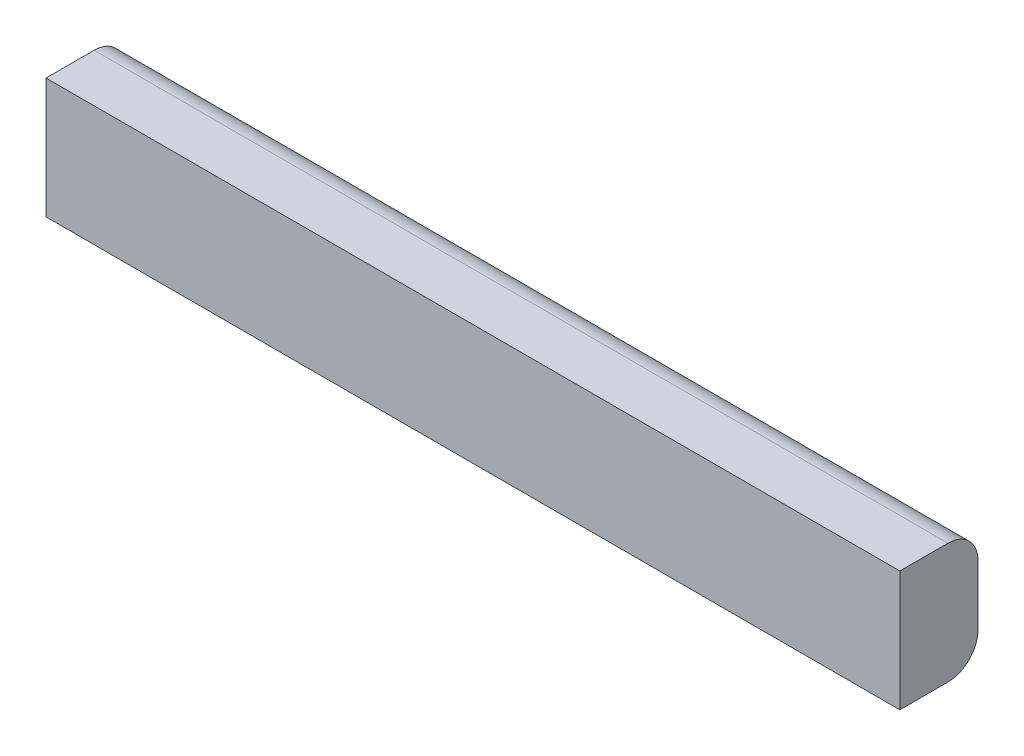
SolidWorks part; units mm, degrees
ref_plane "Front Plane" through (0, 0, 0) normal (0, 0, 1) x (1, 0, 0)
ref_plane "Top Plane" through (0, 0, 0) normal (0, 1, 0) x (1, 0, 0)
ref_plane "Right Plane" through (0, 0, 0) normal (1, 0, 0) x (0, 0, -1)
sketch "Sketch1" plane through (0, 0, 0) normal (1, 0, 0) x (0, 0, -1)
  line L1 (49.3736, 66.0217) -> (-1.4264, 66.0217)
  line L2 (81.1236, 34.2717) -> (81.1236, -29.2283)
  line L3 (49.3736, -60.9783) -> (-1.4264, -60.9783)
  line L4 (-1.4264, 66.0217) -> (-1.4264, -60.9783)
  arc A0 (49.3736, 66.0217) -> (81.1236, 34.2717) centre (49.3736, 34.2717) cw
  arc A1 (81.1236, -29.2283) -> (49.3736, -60.9783) centre (49.3736, -29.2283) cw
  point P8 (81.1236, -60.9783)
  dimension "D3" = 31.75
  dimension "D1" = 127
extrude "Boss-Extrude1" add sketch "Sketch1" along normal mid plane 901.7
equation "\"bumple\"= 24in'bumpler length"
equation "\"D1@Boss-Extrude1\"=\"bumple\""
